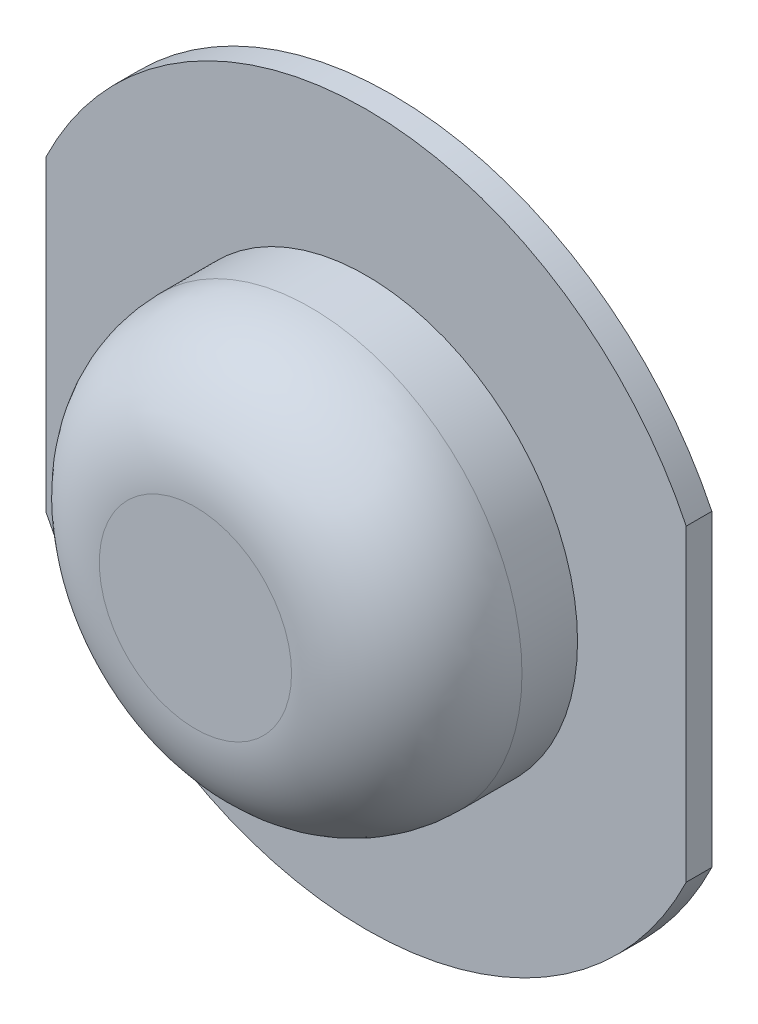
SolidWorks part; units mm, degrees
material "Silicon"
ref_plane "Front Plane" through (0, 0, 0) normal (0, 0, 1) x (1, 0, 0)
ref_plane "Top Plane" through (0, 0, 0) normal (0, 1, 0) x (1, 0, 0)
ref_plane "Right Plane" through (0, 0, 0) normal (1, 0, 0) x (0, 0, -1)
ref_axis "Axis1" through (0, 0, 0) along (0, 0, 1)
sketch "Sketch1" plane through (0, 0, 0) normal (0, 0, 1) x (1, 0, 0)
  line L0 (50, 24.0884) -> (50, -24.0884)
  line L1 (-50, 24.0884) -> (-50, -24.0884)
  arc A0 (-50, -24.0884) -> (50, -24.0884) centre (0, 0) ccw
  arc A1 (50, 24.0884) -> (-50, 24.0884) centre (0, 0) ccw
  dimension "D1" = 55.5
  dimension "D2" = 100
extrude "Boss-Extrude1" add sketch "Sketch1" along normal blind 4
sketch "Sketch5" plane through (0, 0, 0) normal (0, 0, 1) x (1, 0, 0)
  line L0 (0, 0) -> (0, -41.75) construction
  line L1 (43.25, 43.25) -> (-43.25, 43.25) construction
  line L2 (43.25, 43.25) -> (43.25, -43.25) construction
  line L3 (43.25, -43.25) -> (-43.25, -43.25) construction
  line L4 (-43.25, 43.25) -> (-43.25, -43.25) construction
  line L5 (43.25, 43.25) -> (-43.25, -43.25) construction
  line L6 (43.25, -43.25) -> (-43.25, 43.25) construction
  line L7 (0, 0) -> (0, 41.75) construction
  line L8 (0, 0) -> (-41.75, 0) construction
  line L9 (0, 0) -> (41.75, 0) construction
  line L11 (-36, 36) -> (36, 36) construction
  line L12 (-36, 36) -> (-36, -36) construction
  line L13 (-36, -36) -> (36, -36) construction
  line L14 (36, 36) -> (36, -36) construction
  line L15 (-36, 36) -> (36, -36) construction
  line L16 (-36, -36) -> (36, 36) construction
  circle A0 centre (18.497, -18.497) radius 24.753 construction
  circle A1 centre (-18.497, -18.497) radius 24.753 construction
  circle A2 centre (18.497, 18.497) radius 24.753 construction
  circle A3 centre (-18.497, 18.497) radius 24.753 construction
  spline S0 degree 3 poles (45.3558, 18.4579) (39.9657, 0) (45.3558, -18.4579) (38.0677, -38.0677) (18.4579, -45.3558) (0, -39.9657) (-18.4579, -45.3558) (-38.0677, -38.0677) (-45.3558, -18.4579) (-39.9657, 0) (-45.3558, 18.4579) (-38.0677, 38.0677) (-18.4579, 45.3558) (0, 39.9657) (18.4579, 45.3558) (38.0677, 38.0677) (45.3558, 18.4579) (39.9657, 0) (45.3558, -18.4579) knots -0.188146 -0.125 -0.061854 0 0.061854 0.125 0.188146 0.25 0.311854 0.375 0.438146 0.5 0.561854 0.625 0.688146 0.75 0.811854 0.875 0.938146 1 1.061854 1.125 1.188146 only from (41.75, 0) to (41.75, 0)
  point P0 (0, 0)
  dimension "D1" = 86.5
  dimension "D2" = 83.5
  dimension "D3" = 72
extrude "Boss-Extrude2" [suppressed] add sketch "Sketch5" along normal blind 29.78 draft 4
fillet "Fillet1" [suppressed] radius 12
sketch "Sketch6" plane through (0, 0, 0) normal (0, 0, -1) x (-1, 0, 0)
  line L1 (-26.27, -26.27) -> (26.27, -26.27)
  line L2 (-26.27, -26.27) -> (-26.27, 26.27)
  line L3 (-26.27, 26.27) -> (26.27, 26.27)
  line L4 (26.27, -26.27) -> (26.27, 26.27)
  line L5 (-26.27, -26.27) -> (26.27, 26.27) construction
  line L6 (-26.27, 26.27) -> (26.27, -26.27) construction
  point P0 (0, 0)
  dimension "D1" = 52.54
extrude "Cut-Extrude2" cut sketch "Sketch6" against normal blind 2.35
sketch "Sketch7" plane through (0, 0, 0) normal (0, 1, 0) x (1, 0, 0)
  line L0 (0, -2.35) -> (0, -27.35)
  line L1 (26.27, -2.35) -> (-26.27, -2.35) construction
  line L2 (0, -2.35) -> (25, -2.35)
  arc A0 (0, -27.35) -> (25, -2.35) centre (0, -2.35) ccw
  dimension "D1" = 25
revolve "Cut-Revolve1" cut sketch "Sketch7" angle 360 about L0
sketch "Sketch8" plane through (0, 0, 2.35) normal (0, 0, -1) x (-1, 0, 0)
  line L0 (19.5512, 19.5512) -> (-19.5512, -19.5512) construction
  line L1 (-26.27, 26.27) -> (-26.27, -26.27) construction
  line L3 (-19.887, -15.1494) -> (-15.1494, -19.887)
  line L4 (-19.887, -15.1494) -> (-22.5387, -17.8011)
  line L5 (-22.5387, -20.6295) -> (-20.6295, -22.5387)
  line L6 (-15.1494, -19.887) -> (-17.8011, -22.5387)
  line L7 (-19.887, -15.1494) -> (-19.2153, -23.9529) construction
  line L8 (-23.9529, -19.2153) -> (-15.1494, -19.887) construction
  circle A0 centre (0, 0) radius 25 construction
  arc A1 (-22.5387, -17.8011) -> (-22.5387, -20.6295) centre (-21.1245, -19.2153) ccw
  arc A2 (-20.6295, -22.5387) -> (-17.8011, -22.5387) centre (-19.2153, -21.1245) ccw
  point P4 (0, 0)
  point P45 (0, 0)
  dimension "D4" = 2
  dimension "D1" = 45
  dimension "D2" = 5.75
  dimension "D3" = 6.7
extrude "Cut-Extrude3" cut sketch "Sketch8" against normal blind 0.8
pattern_circular "CirPattern1" count 4 over 360 about axis through (0, 0, 0) along (0, 0, 1) of "Cut-Extrude3"
sketch "Sketch9" plane through (0, 0, 4) normal (0, 0, 1) x (1, 0, 0)
  circle A0 centre (0, 0) radius 33.02
  dimension "D1" = 66.04
extrude "Boss-Extrude3" add sketch "Sketch9" along normal blind 26.68
fillet "Fillet2" radius 18 1 edges at (33.02, 0, 30.68)
sketch "Sketch10" plane through (0, 0, 0) normal (0, 0, -1) x (-1, 0, 0)
  line L0 (50, -24.0884) -> (-50, 24.0884) construction
  point P4 (0, 0)
